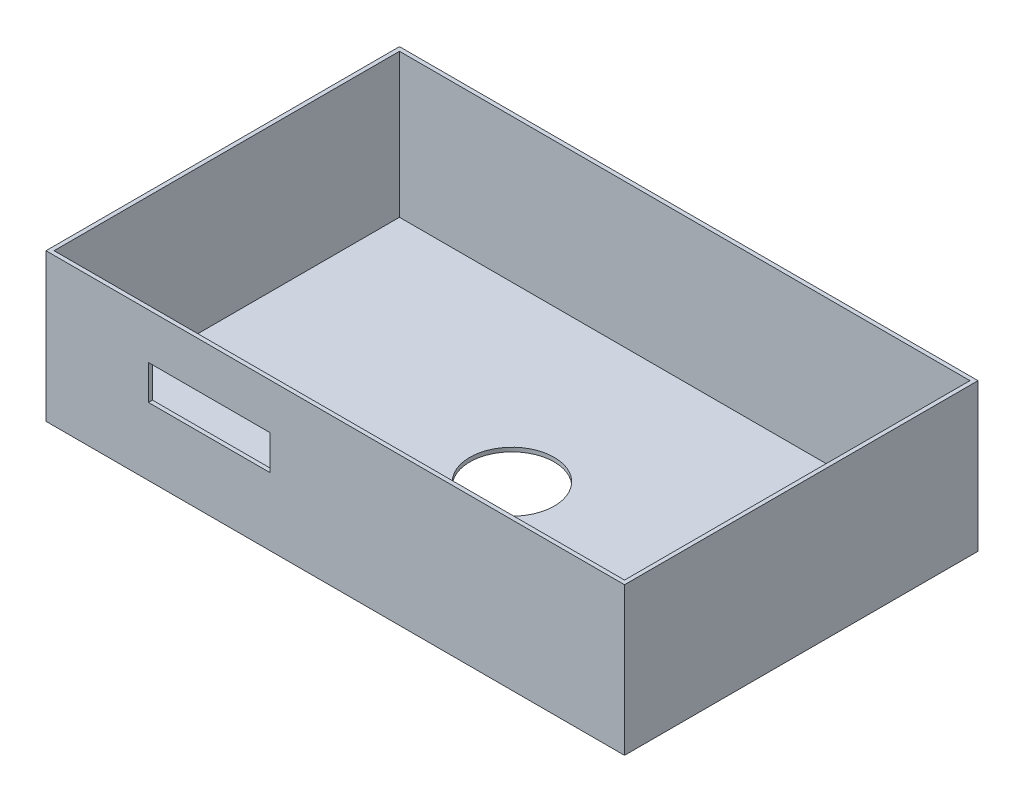
SolidWorks part; units mm, degrees
ref_plane "Front Plane" through (0, 0, 0) normal (0, 0, 1) x (1, 0, 0)
ref_plane "Top Plane" through (0, 0, 0) normal (0, 1, 0) x (1, 0, 0)
ref_plane "Right Plane" through (0, 0, 0) normal (1, 0, 0) x (0, 0, -1)
sketch "Sketch1" plane through (0, 0, 0) normal (0, 1, 0) x (1, 0, 0)
  line L1 (0, 0) -> (1370, 0)
  line L2 (0, 0) -> (0, 837.05)
  line L3 (0, 837.05) -> (1370, 837.05)
  line L4 (1370, 0) -> (1370, 837.05)
  dimension "D1" = 1370
  dimension "D2" = 837.05
extrude "Boss-Extrude1" add sketch "Sketch1" along normal blind 350
shell "Shell1" thickness 9.525 removed face at (685, 350, -418.525)
sketch "Sketch3" plane through (0, 0, 0) normal (0, 0, 1) x (1, 0, 0)
  line L1 (242.6, 242.1) -> (530, 242.1)
  line L3 (242.6, 160.1) -> (530, 160.1)
  line L4 (530, 242.1) -> (530, 160.1)
  line L6 (242.6, 242.1) -> (242.6, 160.1)
  line L7 (0, 0) -> (1370, 0) construction
  line L8 (0, 350) -> (0, 0) construction
  dimension "D1" = 82
  dimension "D2" = 160.1
  dimension "D3" = 242.6
  dimension "D4" = 530
extrude "Cut-Extrude1" cut sketch "Sketch3" against normal up to surface (9.525 mm away) up to face at (685, 179.7625, -9.525)
sketch "Sketch7" plane through (0, 0, 0) normal (0, -1, 0) x (1, 0, 0)
  line L0 (685, 0) -> (685, -837.05) construction
  line L1 (0, 0) -> (1370, 0) construction
  line L2 (1370, -837.05) -> (0, -837.05) construction
  circle A0 centre (685, -418.525) radius 100
  dimension "D1" = 200
extrude "Cut-Extrude2" cut sketch "Sketch7" against normal up to next
equation "\"No. Of Teeth\"= 25"
equation "\"Module\"= 1.5"
equation "\"Bore Diameter\"= 10"
equation "\"Pressure Angle\"= 20"
equation "\"Outer Diameter\"= ( \"No. Of Teeth\" + 2 ) * ( \"Module\" )"
equation "\"Pitch diameter\"= \"No. Of Teeth\" * \"Module\""
equation "\"Backlash\"= 0.3 * \"Module\""
equation "\"Arc Length\"= ( ( \"Module\" * pi ) / 2 ) + \"Backlash\""
equation "\"Fillet Radius\"= 0.38 * \"Module\""
equation "\"Tooth Depth\"= IIF ( \"Module\" <= 1.25 , \"Module\" * 2.4 , \"Module\" * 2.25 )"
